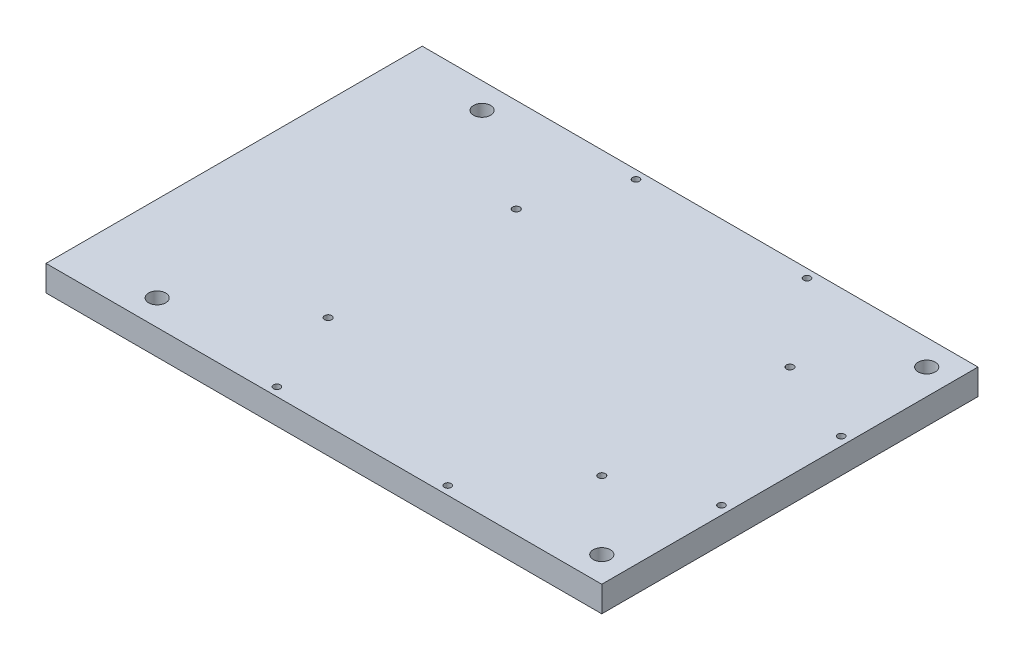
SolidWorks part; units mm, degrees
ref_plane "Front Plane" through (0, 0, 0) normal (0, 0, 1) x (1, 0, 0)
ref_plane "Top Plane" through (0, 0, 0) normal (0, 1, 0) x (1, 0, 0)
ref_plane "Right Plane" through (0, 0, 0) normal (1, 0, 0) x (0, 0, -1)
sketch "Sketch2" plane through (0, 0, 0) normal (0, 1, 0) x (1, 0, 0)
  line L0 (-154.9031, -110) -> (170.0969, -110)
  line L7 (-154.9031, 110) -> (-154.9031, -110)
  line L22 (170.0969, -110) -> (170.0969, 110)
  line L24 (70.8088, -52.5) -> (63.3088, -52.5)
  line L25 (70.8088, -60) -> (70.8088, -52.5)
  line L26 (170.0969, 0) -> (170.0969, 35)
  line L27 (70.8088, 60) -> (50.8088, 60)
  line L28 (-154.9031, 110) -> (170.0969, 110)
  line L29 (170.0969, 35) -> (165.0969, 35)
  line L30 (70.8088, -60) -> (70.8088, 60)
  line L31 (-99.1912, -60) -> (-99.1912, 0)
  line L32 (50.8088, -60) -> (-99.1912, -60)
  line L33 (-99.1912, 60) -> (50.8088, 60)
  line L34 (-99.1912, 0) -> (-99.1912, 60)
  line L35 (50.8088, -60) -> (70.8088, -60)
  circle A11 centre (155.0969, -95) radius 5
  circle A13 centre (155.0969, 95) radius 5
  circle A14 centre (-104.9031, -95) radius 5
  circle A20 centre (-104.9031, 95) radius 5
  circle A21 centre (-24.9031, 105) radius 2
  circle A23 centre (75.0969, -105) radius 2
  circle A24 centre (-24.9031, -105) radius 2
  circle A25 centre (165.0969, 35) radius 2
  circle A26 centre (165.0969, -35) radius 2
  circle A31 centre (63.3088, 52.5) radius 5
  circle A32 centre (-91.6912, 52.5) radius 5
  circle A33 centre (-91.6912, -52.5) radius 5
  circle A34 centre (63.3088, -52.5) radius 5
  circle A35 centre (75.0969, 105) radius 2
extrude "Boss-Extrude3" add sketch "Sketch2" against normal blind 15 contours A11 | L7 L0 L22 L28 | A14 | A20 | A13 region at (155.0969, 0, 95)
sketch "Sketch11" plane through (0, -15, 0) normal (0, -1, 0) x (1, 0, 0)
  line L43 (140.0969, 80) -> (140.0969, 95)
  line L74 (155.0969, -80) -> (155.0969, -5)
  line L75 (155.0969, 5) -> (155.0969, 80)
  line L76 (140.0969, 95) -> (135.0969, 95)
  line L78 (140.0969, 80) -> (155.0969, 80)
  line L79 (155.0969, -80) -> (140.0969, -80)
  line L81 (140.0969, -95) -> (135.0969, -95)
  line L82 (85.0969, -95) -> (85.0969, -5)
  line L83 (85.0969, 95) -> (85.0969, 5)
  line L84 (85.0969, -5) -> (155.0969, -5)
  line L85 (85.0969, 5) -> (155.0969, 5)
  line L86 (85.0969, 95) -> (135.0969, 95)
  line L87 (-134.9031, -80) -> (-84.9031, -80)
  line L88 (-134.9031, -80) -> (-134.9031, -5)
  line L89 (-134.9031, -5) -> (-84.9031, -5)
  line L90 (-84.9031, -80) -> (-84.9031, -5)
  line L91 (-134.9031, 5) -> (-84.9031, 5)
  line L92 (-134.9031, 5) -> (-134.9031, 80)
  line L93 (-134.9031, 80) -> (-84.9031, 80)
  line L94 (-84.9031, 5) -> (-84.9031, 80)
  line L95 (-74.9031, -95) -> (-4.9031, -95)
  line L96 (-74.9031, -95) -> (-74.9031, -5)
  line L97 (-74.9031, -5) -> (-4.9031, -5)
  line L98 (-4.9031, -95) -> (-4.9031, -5)
  line L99 (5.0969, -95) -> (75.0969, -95)
  line L100 (5.0969, -95) -> (5.0969, -5)
  line L101 (5.0969, -5) -> (75.0969, -5)
  line L102 (75.0969, -95) -> (75.0969, -5)
  line L103 (-74.9031, 5) -> (-4.9031, 5)
  line L104 (-74.9031, 5) -> (-74.9031, 95)
  line L105 (-74.9031, 95) -> (-4.9031, 95)
  line L106 (-4.9031, 5) -> (-4.9031, 95)
  line L107 (5.0969, 5) -> (75.0969, 5)
  line L108 (5.0969, 5) -> (5.0969, 95)
  line L109 (5.0969, 95) -> (75.0969, 95)
  line L110 (75.0969, 5) -> (75.0969, 95)
  line L111 (85.0969, -95) -> (135.0969, -95)
  line L112 (140.0969, -80) -> (140.0969, -95)
sketch "Sketch12" plane through (-154.9031, 0, 0) normal (-1, 0, 0) x (0, 0, 1)
  circle A0 centre (-102.5, -7.5) radius 3
  circle A1 centre (0, -7.5) radius 3
  circle A2 centre (102.5, -7.5) radius 3
  dimension "D1" = 3
extrude "Cut-Extrude6" cut sketch "Sketch11" against normal blind 5 contours L99 L102 L101 L100 | L95 L98 L97 L96 | L87 L90 L89 L88 | L91 L94 L93 L92 | L103 L106 L105 L104 | L107 L110 L109 L108 | L86 L83 L85 L75 L78 L43 L76 | L111 L81 L112 L79 L74 L84 L82 region at (119.0784, -15, 48.6111) region at (-109.9031, -15, -42.5) region at (-109.9031, -15, 42.5) region at (-39.9031, -15, -50) region at (40.0969, -15, -50) region at (-39.9031, -15, 50) region at (40.0969, -15, 50)
fillet "Fillet1" radius 5 35 edges at (5.0969, -12.5, -5) (-74.9031, -12.5, -5) (-134.9031, -12.5, -5) (-134.9031, -12.5, 80) (-74.9031, -12.5, 95) (5.0969, -12.5, 95) (85.0969, -12.5, 5) (5.0969, -12.5, 5) (-74.9031, -12.5, 5) (-134.9031, -12.5, 5) (-134.9031, -12.5, -80) (-74.9031, -12.5, -95) (5.0969, -12.5, -95) (75.0969, -12.5, -95) (-4.9031, -12.5, -95) (-84.9031, -12.5, -80) (-84.9031, -12.5, 5) (-4.9031, -12.5, 5) (75.0969, -12.5, 5) (155.0969, -12.5, 5) (140.0969, -12.5, 80) (155.0969, -12.5, 80) (140.0969, -12.5, 95) (75.0969, -12.5, 95) (-4.9031, -12.5, 95) (-84.9031, -12.5, 80) (-84.9031, -12.5, -5) (-4.9031, -12.5, -5) (75.0969, -12.5, -5) (155.0969, -12.5, -5) (85.0969, -12.5, -5) (85.0969, -12.5, -95) (140.0969, -12.5, -95) (155.0969, -12.5, -80) (140.0969, -12.5, -80)
sketch "Sketch20" plane through (0, -15, 0) normal (0, -1, 0) x (1, 0, 0)
  line L0 (-154.9031, 110) -> (-154.9031, 105)
  line L1 (-154.9031, -110) -> (-154.9031, 110) construction
  circle A1 centre (75.0969, 105) radius 2
  circle A3 centre (-24.9031, 105) radius 2
  circle A4 centre (-24.9031, -105) radius 2
  circle A5 centre (75.0969, -105) radius 2
  circle A6 centre (165.0969, -35) radius 2
  circle A7 centre (165.0969, 35) radius 2
hole_wizard "CSK for M4 Countersunk Flat Head Screw2" positions "Sketch26" profile "Sketch28" countersink size "M4" standard "ISO" end condition through all
sketch "Sketch26" plane through (0, -15, 0) normal (0, -1, 0) x (-1, 0, 0)
  point P0 (24.9031, 105)
  point P3 (-75.0969, 105)
  point P6 (-165.0969, 35)
  point P9 (-165.0969, -35)
  point P12 (-75.0969, -105)
  point P15 (24.9031, -105)
sketch "Sketch28" plane through (-24.9031, -15, -105) normal (1, 0, 0) x (0, 0, -1)
  line L0 (0, 0) -> (0, 15)
  line L1 (0, 15) -> (2, 15)
  line L2 (2, 15) -> (2, 2.2)
  line L3 (2, 2.2) -> (3.7, 0.5)
  line L4 (3.7, 0.5) -> (3.7, 0)
  line L6 (3.7, 0) -> (0, 0)
  line L7 (-2, 2.2) -> (-3.7, 0.5) construction
  line L11 (0, -6.35) -> (0, 107.95) construction
  dimension "Thru Hole Dia." = 4
  dimension "Thru Hole Depth" = 15
  dimension "C'Sink Dia." = 7.4
  dimension "C'Sink Angle" = 90
  dimension "Head Clearance" = 0.5
sketch "Sketch39" plane through (0, 0, 0) normal (0, 1, 0) x (1, 0, 0)
  circle A4 centre (115.0969, 55) radius 3
  circle A5 centre (-44.9031, 55) radius 3
  circle A6 centre (-44.9031, -55) radius 3
  circle A7 centre (115.0969, -55) radius 3
  dimension "D1" = 2
  dimension "D2" = 2
hole_wizard "M5 Tapped Hole2" positions "Sketch46" profile "Sketch47" tap size "M5" standard "ISO"
sketch "Sketch46" plane through (0, 0, 0) normal (0, 1, 0) x (1, 0, 0)
  point P0 (115.0969, 55)
  point P3 (115.0969, -55)
  point P6 (-44.9031, -55)
  point P9 (-44.9031, 55)
sketch "Sketch47" plane through (115.0969, 0, -55) normal (1, 0, 0) x (0, 0, 1)
  line L0 (0, 0) -> (0, 6.2618)
  line L1 (0, 6.2618) -> (2.1, 5)
  line L2 (2.1, 5) -> (2.1, 0)
  line L5 (2.1, 0) -> (0, 0)
  line L10 (0, 6.2618) -> (-2.1, 5) construction
  line L11 (0, -6.35) -> (0, 107.95) construction
  dimension "Tap Drill Dia." = 4.2
  dimension "Tap Drill Depth" = 5
  dimension "Drill Angle" = 118
cosmetic thread "Hole Thread17" parameters "D1"=5, "D2"=5
cosmetic thread "Hole Thread18" parameters "D1"=5, "D2"=5
cosmetic thread "Hole Thread19" parameters "D1"=5, "D2"=5
cosmetic thread "Hole Thread20" parameters "D1"=5, "D2"=5
hole_wizard "M6 Tapped Hole3" positions "Sketch48" profile "Sketch49" tap size "M6" standard "ISO"
sketch "Sketch48" plane through (-154.9031, 0, 0) normal (-1, 0, 0) x (0, 0, 1)
  point P0 (-102.5, -7.5)
  point P3 (0, -7.5)
  point P6 (102.5, -7.5)
sketch "Sketch49" plane through (-154.9031, -7.5, -102.5) normal (0, 1, 0) x (0, 0, 1)
  line L0 (0, 0) -> (0, 6.5022)
  line L1 (0, 6.5022) -> (2.5, 5)
  line L2 (2.5, 5) -> (2.5, 0)
  line L5 (2.5, 0) -> (0, 0)
  line L10 (0, 6.5022) -> (-2.5, 5) construction
  line L11 (0, -6.35) -> (0, 107.95) construction
  dimension "Tap Drill Dia." = 5
  dimension "Tap Drill Depth" = 5
  dimension "Drill Angle" = 118
cosmetic thread "Hole Thread21" parameters "D1"=4.5, "D2"=6
cosmetic thread "Hole Thread22" parameters "D1"=4.5, "D2"=6
cosmetic thread "Hole Thread23" parameters "D1"=4.5, "D2"=6
